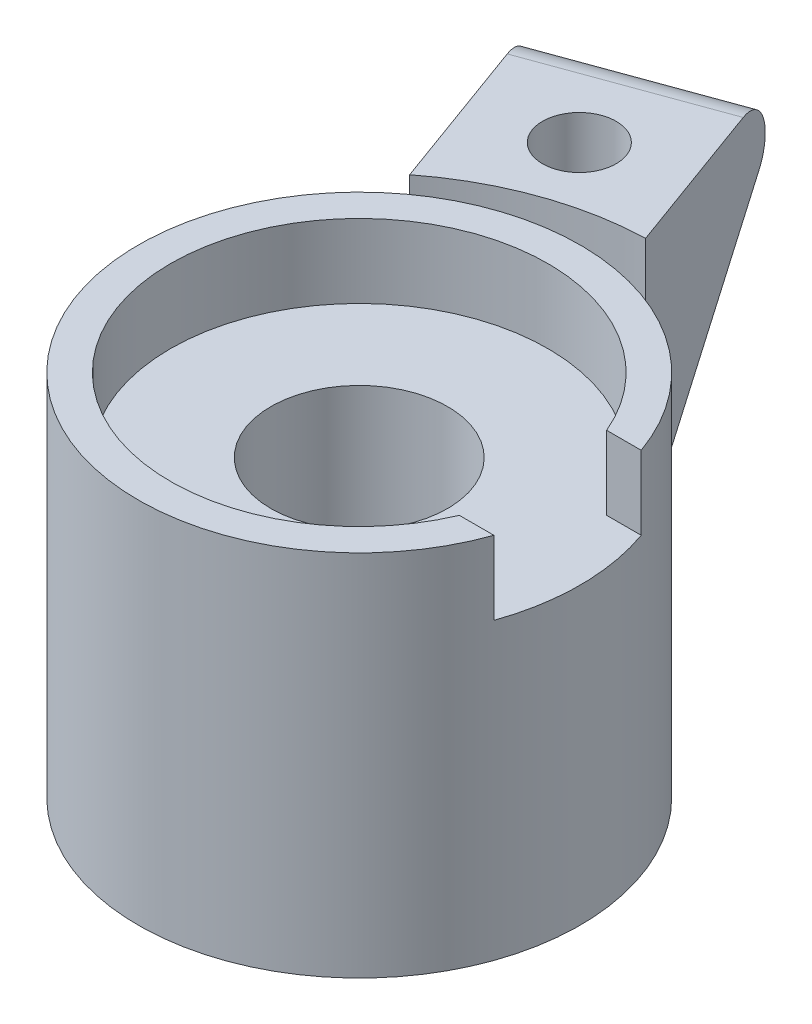
SolidWorks part; units mm, degrees
ref_plane "Front Plane" through (0, 0, 0) normal (0, 0, 1) x (1, 0, 0)
ref_plane "Top Plane" through (0, 0, 0) normal (0, 1, 0) x (1, 0, 0)
ref_plane "Right Plane" through (0, 0, 0) normal (1, 0, 0) x (0, 0, -1)
sketch "Sketch1" plane through (0, 0, 0) normal (0, 1, 0) x (1, 0, 0)
  circle A0 centre (0, 0) radius 12
  circle A1 centre (0, 0) radius 4.8
extrude "Boss-Extrude2" add sketch "Sketch1" against normal blind 20 contours A0 A1 | A1 region at (-11.6606, 0, 0) region at (0, 0, 0)
extrude "Cut-Extrude2" cut sketch "Sketch1<3>" against normal through all contours A1 region at (0, 0, 0)
sketch "Sketch1<3>" plane through (0, 0, 0) normal (0, 1, 0) x (1, 0, 0) same geometry as "Sketch1"
sketch "Sketch3" plane through (0, 0, 0) normal (0, 1, 0) x (1, 0, 0)
  circle A0 centre (0, 0) radius 10.25
extrude "Cut-Extrude3" cut sketch "Sketch3" against normal blind 4
sketch "Sketch5" plane through (0, 0, 0) normal (0, 1, 0) x (1, 0, 0)
  line L0 (-11, 0) -> (11, 0) construction
  line L1 (5.4486, -4) -> (16.4836, -4)
  line L2 (5.4486, -4) -> (5.4486, 4)
  line L3 (5.4486, 4) -> (16.4836, 4)
  line L4 (16.4836, -4) -> (16.4836, 4)
  line L5 (5.4486, -4) -> (16.4836, 4) construction
  line L6 (5.4486, 4) -> (16.4836, -4) construction
  point P0 (10.9661, 0)
  dimension "D1" = 8
extrude "Cut-Extrude5" cut sketch "Sketch5" against normal up to surface (4 mm away) up to face at (0, -4, 10.25)
ref_axis "Axis1" through (0, 1, 0) along (0, -1, 0)
ref_plane "Plane1" through (0, 0, 0) normal (-0.9397, 0, 0.342) x (0, -1, 0)
sketch "Sketch6" plane through (0, 0, 0) normal (-0.9397, 0, 0.342) x (0, -1, 0)
  line L0 (2, -11) -> (20, -11)
  line L1 (20, -11) -> (2, -29)
  line L2 (2, -29) -> (2, -11)
  line L3 (-1, 0) -> (21, 0) construction
  line L4 (20, -12) -> (20, 12) construction
  line L5 (0, 14.1073) -> (0, -14.1073) construction
  dimension "D1" = 11
  dimension "D2" = 45
  dimension "D3" = 2
extrude "Boss-Extrude3" add sketch "Sketch6" along normal blind 5 and the other way blind 5
sketch "Sketch7" plane through (0, 0, 0) normal (0, 1, 0) x (1, 0, 0)
  circle A0 centre (0, 0) radius 12
  circle A1 centre (0, 0) radius 16.1
extrude "Cut-Extrude6" cut sketch "Sketch7" against normal blind 6
sketch "Sketch9" plane through (0, -2, 0) normal (0, 1, 0) x (1, 0, 0)
  line L0 (-4.8922, 13.4411) -> (4.8922, -13.4411) construction
  circle A0 centre (-6.8404, 18.7939) radius 2
  dimension "D1" = 20
extrude "Cut-Extrude7" cut sketch "Sketch9" against normal up to next
fillet "Fillet1" radius 2 1 edges at (-9.9186, -2, -27.2511)
